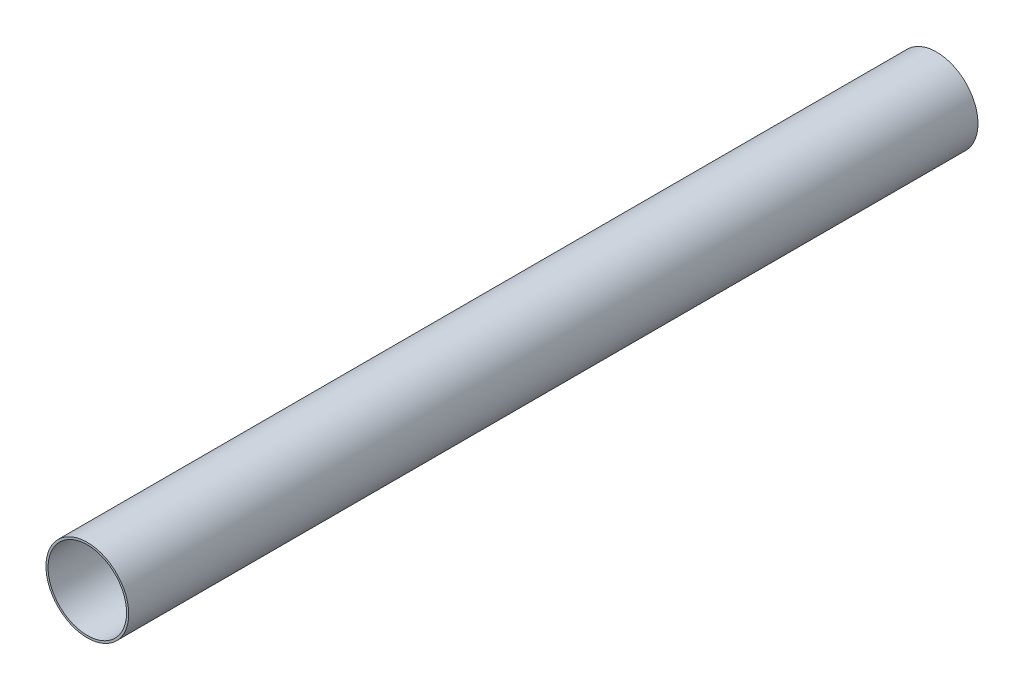
SolidWorks part; units mm, degrees
material "6061-T6 (SS)"
ref_plane "Front Plane" through (0, 0, 0) normal (0, 0, 1) x (1, 0, 0)
ref_plane "Top Plane" through (0, 0, 0) normal (0, 1, 0) x (1, 0, 0)
ref_plane "Right Plane" through (0, 0, 0) normal (1, 0, 0) x (0, 0, -1)
sketch "Sketch1" plane through (0, 0, 0) normal (0, 0, 1) x (1, 0, 0)
  circle A0 centre (0, 0) radius 49
  circle A1 centre (0, 0) radius 46.482
extrude "Extrude1" add sketch "Sketch1" along normal blind 1005.332
